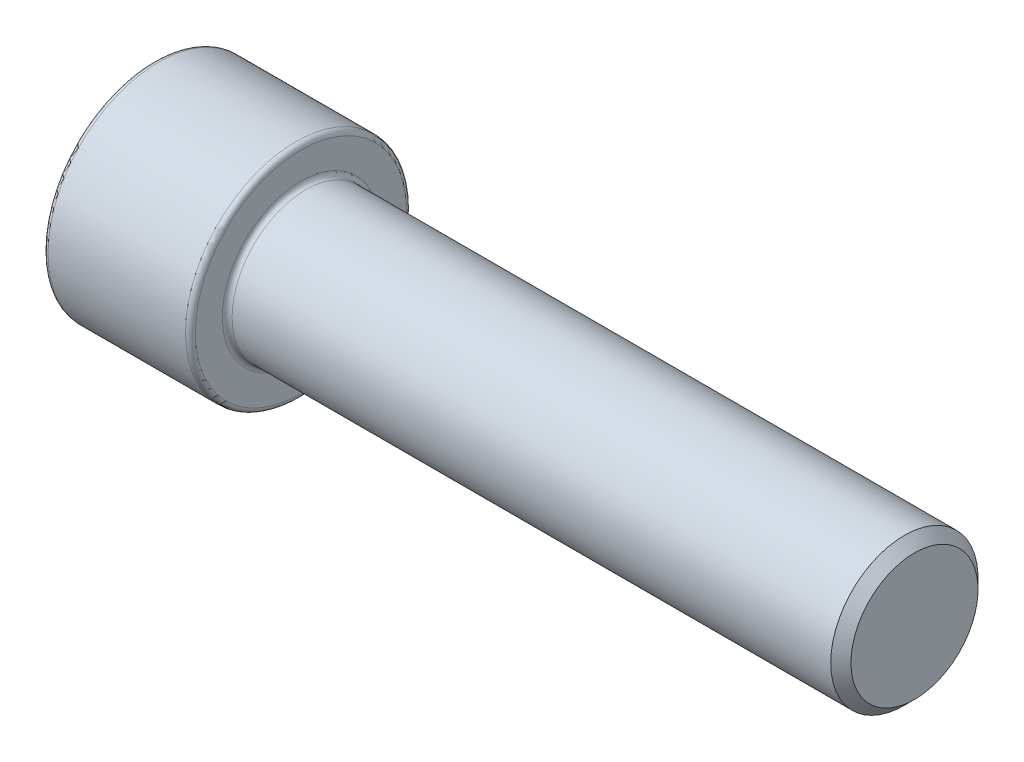
SolidWorks part; units mm, degrees
ref_plane "Front Plane" through (0, 0, 0) normal (0, 0, 1) x (1, 0, 0)
ref_plane "Top Plane" through (0, 0, 0) normal (0, 1, 0) x (1, 0, 0)
ref_plane "Right Plane" through (0, 0, 0) normal (1, 0, 0) x (0, 0, -1)
sketch "BaseHeadSke" plane through (0, 0, 0) normal (1, 0, 0) x (0, 0, -1)
  circle A1 centre (0, 0) radius 18
  dimension "Head_diameter" = 36
extrude "BaseHead" add sketch "BaseHeadSke" along normal blind 24
sketch "BodySke" plane through (0, 0, 0) normal (0, 0, 1) x (1, 0, 0)
  line L0 (0, 0) -> (124, 0)
  line L1 (124, 0) -> (124, 10.352)
  line L2 (124, 10.352) -> (122.352, 12)
  line L3 (122.352, 12) -> (0, 12)
  line L4 (0, 12) -> (0, 0)
  line L6 (0, 0) -> (159.3976, 0) construction
  line L7 (64, -84.3176) -> (64, 77.7215) construction
  line L8 (121, -21.5941) -> (121, 39.2994) construction
  line L10 (24, -18) -> (24, 18) construction
  dimension "Length" = 100
  dimension "Thread_length" = 60
  dimension "Advance" = 3
revolve "BaseBody" add sketch "BodySke" angle 360 about L6
cosmetic thread "ThreadCosmetic" [suppressed] parameters "Thread_length"=60, "Thread_minor"=20.704
sketch "CutSocketSke" plane through (0, 0, 0) normal (1, 0, 0) x (0, 0, -1)
  line L1 (0, 10.9697) -> (-9.5, 5.4848)
  line L2 (-9.5, 5.4848) -> (-9.5, -5.4848)
  line L3 (-9.5, -5.4848) -> (0, -10.9697)
  line L4 (0, -10.9697) -> (9.5, -5.4848)
  line L5 (9.5, -5.4848) -> (9.5, 5.4848)
  line L6 (9.5, 5.4848) -> (0, 10.9697)
  circle A0 centre (0, 0) radius 9.5 construction
extrude "CutSocket" cut sketch "CutSocketSke" along normal blind 12
sketch "CutHoleSke" plane through (0, 0, 0) normal (0, 0, 1) x (1, 0, 0)
  line L0 (0, 0) -> (149.4323, 0) construction
  line L1 (0, 9.5) -> (13.6, 9.5)
  line L2 (13.6, 9.5) -> (19.0848, 0)
  line L3 (19.0848, 0) -> (0, 0)
  line L4 (0, 0) -> (0, 9.5)
  line L6 (24, -18) -> (24, 18) construction
  dimension "D1" = 60
  dimension "Hole_depth" = 10.4
  dimension "D2" = 19
revolve "CutHole" cut sketch "CutHoleSke" angle 360 about L0
fillet "Fillet" radius 0.8 3 edges at (24, 0, -12) (24, 0, -18) (0, 0, -18)
sketch "ThdSchSke" plane through (0, 0, 0) normal (0, 0, 1) x (1, 0, 0)
  line L0 (120.0485, 13.9029) -> (120.0485, 12)
  line L1 (120.0485, 12) -> (121, 10.352)
  line L2 (121, 10.352) -> (121.9515, 12)
  line L3 (121.9515, 12) -> (121.9515, 13.9029)
  line L4 (121.9515, 13.9029) -> (120.0485, 13.9029)
  line L6 (0, 0) -> (141.9934, 0) construction
  line L7 (124, -10.352) -> (124, 10.352) construction
  dimension "D2" = 20.704
  dimension "D3" = 24
  dimension "Advance" = 3
revolve "ThreadSchematic" [suppressed] cut sketch "ThdSchSke" angle 360 about L6
pattern_linear "ThdSchPat" [suppressed] count 19 spacing 3 along (-1, 0, 0) of bodies 107
equation "\"Thread_minor@ThreadCosmetic\" = \"Minor_dia@BodySke\""
equation "\"Thread_length@ThreadCosmetic\" = \"Thread_length@BodySke\""
equation "\"D2@CutHoleSke\" = \"Socket_width@CutSocketSke\""
equation "\"D2@ThdSchSke\" = \"Minor_dia@BodySke\""
equation "\"D3@ThdSchSke\" = \"Diameter@BodySke\""
equation "\"Advance@ThdSchSke\" = \"Advance@BodySke\""
equation "\"D3@ThdSchPat\" = \"Advance@BodySke\""
equation "\"D1@ThdSchPat\" =  int( \"Thread_length@BodySke\"/\"Advance@BodySke\" )-1"
